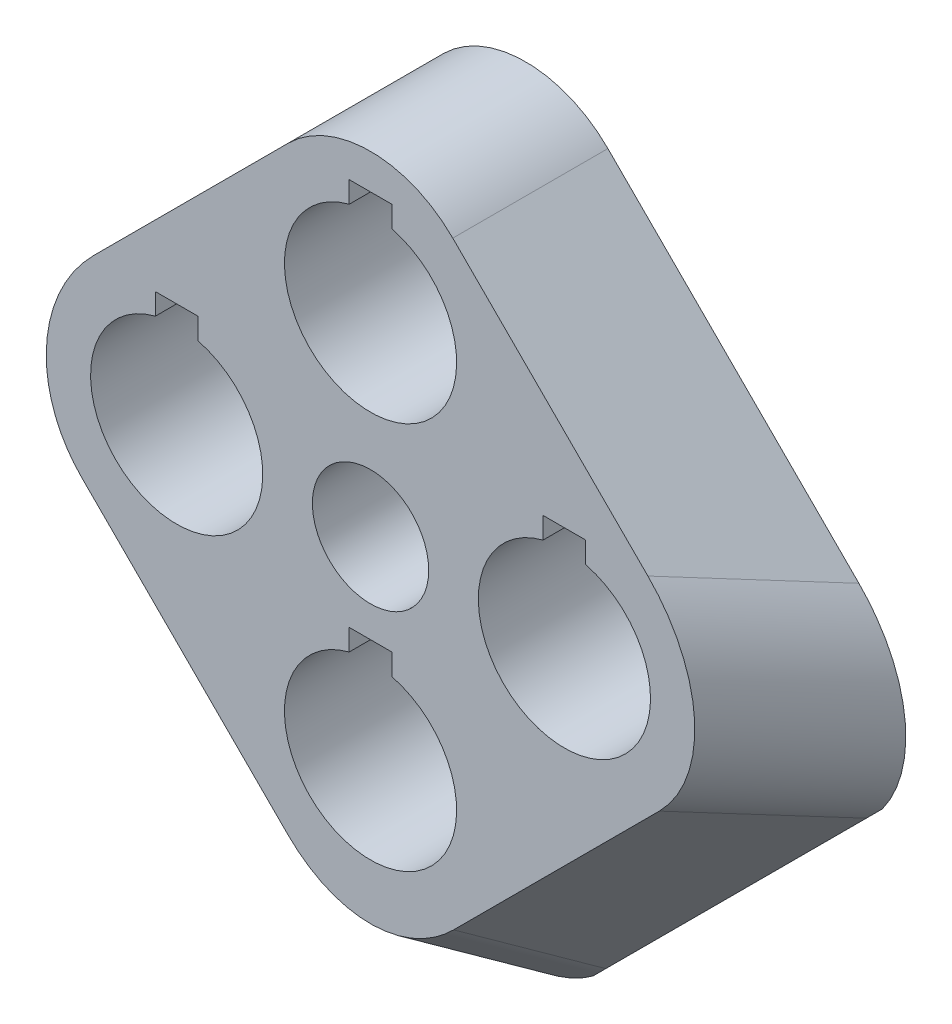
SolidWorks part; units mm, degrees
ref_plane "Front Plane" through (0, 0, 0) normal (0, 0, 1) x (1, 0, 0)
ref_plane "Top Plane" through (0, 0, 0) normal (0, 1, 0) x (1, 0, 0)
ref_plane "Right Plane" through (0, 0, 0) normal (1, 0, 0) x (0, 0, -1)
sketch "Sketch1" plane through (0, 0, 0) normal (0, 0, 1) x (1, 0, 0)
  line L0 (-2.75, 13.504) -> (2.75, 13.504)
  line L1 (0, -24.2553) -> (49.2553, 25)
  line L2 (0, 74.2553) -> (49.2553, 25)
  line L3 (-2.75, 63.504) -> (2.75, 63.504)
  line L4 (-2.75, 13.504) -> (-2.75, 10.754)
  line L5 (2.75, 13.504) -> (2.75, 10.754)
  line L6 (0, 74.2553) -> (-49.2553, 25)
  line L9 (-2.75, 63.504) -> (-2.75, 60.754)
  line L10 (2.75, 63.504) -> (2.75, 60.754)
  line L11 (0, -24.2553) -> (-49.2553, 25)
  line L12 (0, 0) -> (0, 50) construction
  line L13 (0, 25) -> (25, 25) construction
  line L14 (0, 25) -> (-25, 25) construction
  line L15 (22.25, 38.504) -> (27.75, 38.504)
  line L18 (22.25, 38.504) -> (22.25, 35.754)
  line L19 (27.75, 38.504) -> (27.75, 35.754)
  line L21 (-27.75, 38.504) -> (-22.25, 38.504)
  line L24 (-27.75, 38.504) -> (-27.75, 35.754)
  line L25 (-22.25, 38.504) -> (-22.25, 35.754)
  arc A0 (-2.75, 10.754) -> (2.75, 10.754) centre (0, 0) ccw
  circle A1 centre (0, 25) radius 7.5
  arc A2 (-2.75, 60.754) -> (2.75, 60.754) centre (0, 50) ccw
  arc A4 (22.25, 35.754) -> (27.75, 35.754) centre (25, 25) ccw
  arc A6 (-27.75, 35.754) -> (-22.25, 35.754) centre (-25, 25) ccw
extrude "Boss-Extrude1" add sketch "Sketch1" along normal blind 20
fillet "Fillet1" radius 15 4 edges at (0, 74.2553, 10) (-49.2553, 25, 10) (0, -24.2553, 10) (49.2553, 25, 10)
sketch "Sketch5" plane through (0, 0, 0) normal (0, 0, -1) x (-1, 0, 0)
  line L0 (38.6487, 35.6066) -> (56.3264, 17.9289)
  line L1 (-38.6487, 35.6066) -> (-56.3264, 17.9289)
  line L2 (-56.3264, 17.9289) -> (0, -38.3975)
  line L3 (0, -38.3975) -> (56.3264, 17.9289)
  line L4 (-38.6487, 35.6066) -> (-38.6487, 14.3934)
  line L5 (-38.6487, 14.3934) -> (-10.6066, -13.6487)
  line L6 (-10.6066, -13.6487) -> (-38.6487, 14.3934) construction
  line L7 (-10.6066, -13.6487) -> (10.6066, -13.6487)
  line L8 (10.6066, -13.6487) -> (38.6487, 14.3934)
  line L9 (38.6487, 14.3934) -> (38.6487, 35.6066)
extrude "Boss-Extrude2" add sketch "Sketch5" against normal blind 20
chamfer "Chamfer1" distance 10 angle 63 2 edges at (-28.1632, -10.2343, 20) (28.1632, -10.2343, 20) first distance on face at (0, 25.8303, 20)
fillet "Fillet2" radius 17 3 edges at (0, -31.3264, 10.1869) (52.7909, 21.4645, 10.1869) (-52.7909, 21.4645, 10.1869)
